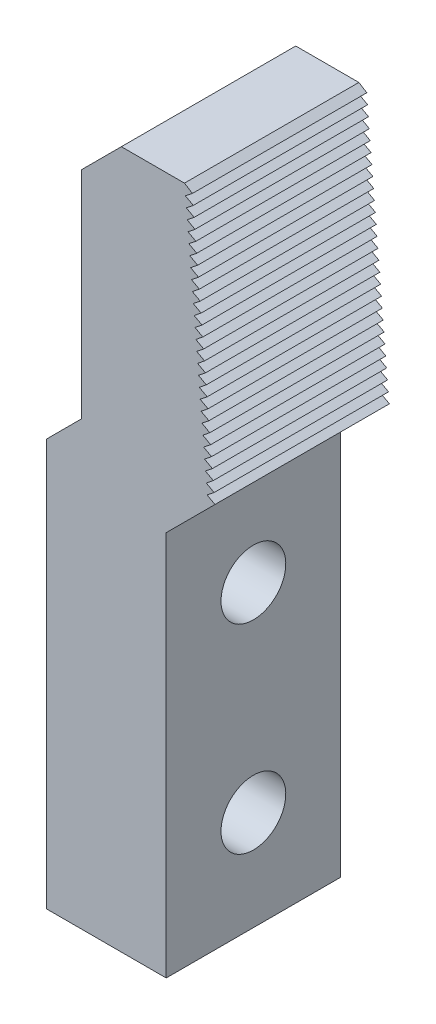
SolidWorks part; units mm, degrees
ref_plane "前视基准面" through (0, 0, 0) normal (0, 0, 1) x (1, 0, 0)
ref_plane "上视基准面" through (0, 0, 0) normal (0, 1, 0) x (1, 0, 0)
ref_plane "右视基准面" through (0, 0, 0) normal (1, 0, 0) x (0, 0, -1)
sketch "草图48" plane through (0, 0, 0) normal (0, 0, 1) x (1, 0, 0)
  line L0 (34.1, 110) -> (36, 110)
  line L1 (0, 0) -> (36, 0)
  line L2 (-0.0001, 170) -> (0, 0)
  line L3 (0, 170) -> (34.1, 170)
  line L4 (36, 0) -> (36, 110)
  line L7 (34.1, 110) -> (34.1, 144.543)
  line L9 (34.1, 144.543) -> (34.1, 170)
  line L10 (0, 170) -> (-0.0001, 170)
  line L11 (0, 170) -> (36, 170) construction
  line L12 (0, 110) -> (36, 110) construction
  dimension "D2" = 36
  dimension "D5" = 60
  dimension "D6" = 1.9
  dimension "D3" = 110
extrude "拉伸1" add sketch "草图48" along normal blind 35
sketch "草图49" plane through (0, 0, 35) normal (0, 0, 1) x (1, 0, 0)
  line L1 (34.1, 113.7) -> (29.1744, 170)
  line L5 (34.1, 110) -> (34.1, 170) construction
  line L6 (34.1, 170) -> (29.1744, 170)
  line L8 (34.1, 170) -> (34.1, 113.7)
  dimension "D2" = 5
  dimension "D1" = 56.3
extrude "切除-拉伸28" cut sketch "草图49" against normal blind 49
sketch "草图50" plane through (0, 0, 35) normal (0, 0, 1) x (1, 0, 0)
  line L0 (27.6687, 170) -> (29.2615, 169.0038)
  line L1 (29.1744, 170) -> (-0.0001, 170) construction
  line L2 (29.1744, 170) -> (34.1, 113.7) construction
  line L3 (29.2615, 169.0038) -> (29.1744, 170)
  line L4 (29.1744, 170) -> (27.6687, 170)
  dimension "D1" = 1
  dimension "D2" = 1.5057
extrude "切除-拉伸29" cut sketch "草图50" against normal through all
sketch "草图51" plane through (0, 0, 35) normal (0, 0, 1) x (1, 0, 0)
  line L0 (27.8544, 167.8769) -> (29.2615, 169.0038)
  line L1 (27.8544, 167.8769) -> (29.4359, 167.0114)
  line L2 (29.2615, 169.0038) -> (34.1, 113.7) construction
  line L3 (29.2615, 169.0038) -> (29.4359, 167.0114)
  dimension "D1" = 2
  dimension "D2" = 1.5
  dimension "D3" = 67.38
extrude "切除-拉伸30" cut sketch "草图51" against normal blind 49
pattern_linear "阵列(线性)1" count 26 spacing 2 along (0.0872, -0.9962, 0) of "切除-拉伸30"
chamfer "倒角2" distance 3.4 angle 45 1 edges at (36, 110, 17.5)
sketch "草图54" plane through (36, 0, 0) normal (1, 0, 0) x (0, 0, -1)
  line L0 (-35, 0) -> (-35, 106.6) construction
  line L1 (0, 0) -> (-35, 0)
  line L2 (0, 0) -> (0, 30)
  line L3 (0, 30) -> (-35, 30)
  line L4 (-35, 0) -> (-35, 30)
extrude "切除-拉伸33" cut sketch "草图54" against normal blind 50
sketch "草图56" plane through (0, 0, 35) normal (0, 0, 1) x (1, 0, 0)
  line L1 (29, 106.6) -> (33.7936, 117.2017)
  line L2 (29, 30) -> (29, 106.6)
  line L3 (29, 30) -> (29, 106.6)
  line L4 (33.7936, 117.2017) -> (59.3243, 70.8297)
  line L5 (59.3243, 70.8297) -> (36, 30)
  line L6 (36, 30) -> (29, 30)
  dimension "D1" = 7
extrude "切除-拉伸34" cut sketch "草图56" against normal blind 110
chamfer "倒角3" distance 15 angle 45 1 edges at (-0.0001, 170, 17.5)
sketch "草图61" plane through (0, 0, 0) normal (-1, 0, 0) x (0, 0, 1)
  line L0 (0, 30) -> (35, 30) construction
  circle A0 centre (17.5, 50) radius 6.5
  circle A1 centre (17.5, 90) radius 6.5
  dimension "D1" = 20
extrude "切除-拉伸37" cut sketch "草图61" against normal blind 100
sketch "草图62" plane through (0, 0, 35) normal (0, 0, 1) x (1, 0, 0)
  line L0 (33.7936, 117.2017) -> (24, 107.408)
  line L1 (24, 107.408) -> (24, 30)
  line L2 (0, 30) -> (29, 30) construction
  line L3 (24, 30) -> (29, 30)
  line L4 (29, 30) -> (29, 106.6)
  line L5 (29, 106.6) -> (33.7936, 117.2017)
  dimension "D1" = 5
  dimension "D2" = 135
extrude "切除-拉伸38" cut sketch "草图62" against normal through all
sketch "草图63" plane through (0, 0, 35) normal (0, 0, 1) x (1, 0, 0)
  line L0 (33.7936, 117.2017) -> (24, 107.408) construction
  line L1 (-0.0001, 155) -> (0, 30) construction
  line L2 (-0.0001, 111.6922) -> (6.9999, 118.6922)
  line L11 (-0.0001, 111.6922) -> (-12.7432, 111.6922)
  line L12 (6.9999, 118.6922) -> (6.9999, 179.6209)
  line L13 (6.9999, 179.6209) -> (-0.0001, 176.6616)
  line L14 (-12.7432, 111.6922) -> (-12.7432, 177.3913)
  line L15 (-12.7432, 177.3913) -> (-0.0001, 176.6616)
  dimension "D1" = 20
extrude "切除-拉伸39" cut sketch "草图63" against normal through all
